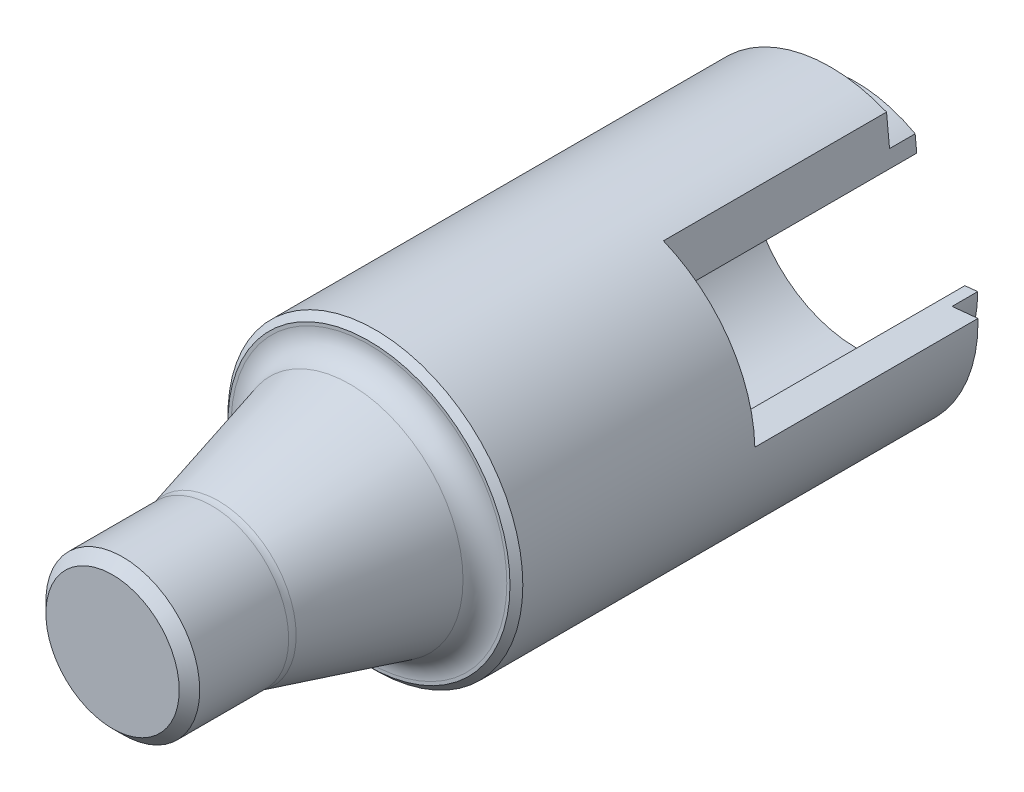
SolidWorks part; units mm, degrees
material "PET"
ref_plane "Front Plane" through (0, 0, 0) normal (0, 0, 1) x (1, 0, 0)
ref_plane "Top Plane" through (0, 0, 0) normal (0, 1, 0) x (1, 0, 0)
ref_plane "Right Plane" through (0, 0, 0) normal (1, 0, 0) x (0, 0, -1)
sketch "Sketch1" plane through (0, 0, 0) normal (0, 0, 1) x (1, 0, 0)
  circle A2 centre (0, 0) radius 30.0863
  circle A3 centre (0, 0) radius 30.0863
  dimension "D1" = 1.27
extrude "Boss-Extrude1" add sketch "Sketch1" against normal blind 95.25
sketch "Sketch2" plane through (0, 0, 0) normal (0, 0, 1) x (1, 0, 0)
  circle A0 centre (0, 0) radius 36.5125 construction
  circle A1 centre (0, 0) radius 36.5125
extrude "Boss-Extrude2" add sketch "Sketch2" along normal blind 25.4 and the other way offset from surface 6.35 other way up to face at (30.0863, 0, -95.25)
sketch "Sketch3" plane through (0, 0, 25.4) normal (0, 0, 1) x (1, 0, 0)
  circle A0 centre (0, 0) radius 19.05
  dimension "D1" = 38.1
extrude "Boss-Extrude3" add sketch "Sketch3" along normal blind 38.1
draft "Draft1" type of draft neutral plane draft angle 15 faces to draft 1 face at (19.05, 0, 63.5) neutral plane through (0, 0, 63.5) neutral plane normal (0, 0, 1) parameters "D1"=15
sketch "Sketch4" plane through (0, 0, 63.5) normal (0, 0, 1) x (1, 0, 0)
  circle A1 centre (0, 0) radius 19.05
  circle A2 centre (0, 0) radius 19.05
  dimension "D1" = 0
extrude "Boss-Extrude4" add sketch "Sketch4" along normal blind 25.4
chamfer "Chamfer1" distance 2.54 angle 45 1 edges at (19.05, 0, 88.9)
fillet "Fillet1" radius 6.35 2 edges at (29.2589, 0, 25.4) (19.05, 0, 63.5)
chamfer "Chamfer2" distance 1.5875 angle 45 1 edges at (36.5125, 0, 25.4)
sketch "Sketch5" plane through (0, 0, -95.25) normal (0, 0, -1) x (-1, 0, 0)
  circle A0 centre (0, 0) radius 26.9113
  circle A1 centre (0, 0) radius 30.0863 construction
  point P4 (0, 0)
  dimension "D1" = 3.175
extrude "Cut-Extrude1" cut sketch "Sketch5" against normal up to surface (120.65 mm away) up to face at (34.925, 0, 25.4)
sketch "Sketch6" plane through (0, 0, 25.4) normal (0, 0, -1) x (-1, 0, 0)
  circle A0 centre (0, 0) radius 15.875
  circle A1 centre (0, 0) radius 19.05 construction
  circle A2 centre (0, 0) radius 16.51 construction
  dimension "D1" = 3.175
extrude "Cut-Extrude2" cut sketch "Sketch6" against normal offset from surface (60.325 mm away) 3.175 up to face at (16.51, 0, 88.9)
sketch "Sketch9" plane through (0, 0, -95.25) normal (0, 0, -1) x (-1, 0, 0)
  line L0 (-17.3073, -1.0596) -> (-37.8448, 0.9697)
  line L1 (-37.8448, 0.9697) -> (-33.9423, 40.4648)
  line L2 (-33.9423, 40.4648) -> (-13.4048, 38.4355)
  line L3 (-13.4048, 38.4355) -> (-17.3073, -1.0596)
extrude "Cut-Extrude3" cut sketch "Sketch9" against normal blind 61.595
